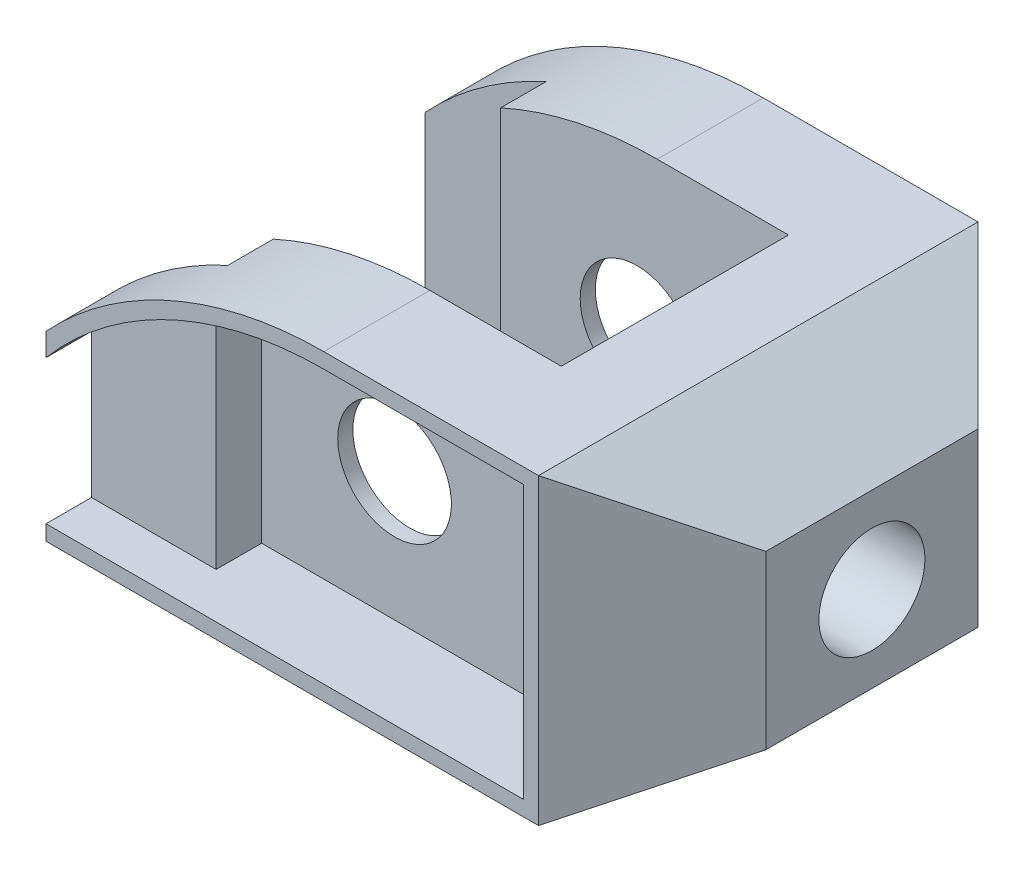
SolidWorks part; units mm, degrees
material "1060 Alloy"
ref_plane "Front Plane" through (0, 0, 0) normal (0, 0, 1) x (1, 0, 0)
ref_plane "Top Plane" through (0, 0, 0) normal (0, 1, 0) x (1, 0, 0)
ref_plane "Right Plane" through (0, 0, 0) normal (1, 0, 0) x (0, 0, -1)
sketch "Sketch1" plane through (0, 0, 0) normal (0, 0, 1) x (1, 0, 0)
  line L0 (0, 0) -> (65, 0)
  line L1 (65, 0) -> (80, 8.6603)
  line L2 (80, 8.6603) -> (80, 31.3397)
  line L3 (80, 31.3397) -> (65, 40)
  line L4 (65, 40) -> (36.6606, 40)
  line L5 (0, 24) -> (0, 0)
  arc A0 (36.6606, 40) -> (0, 24) centre (36.6606, -10) ccw
  circle A1 centre (34, 19) radius 7.5
  dimension "D7" = 50
  dimension "D10" = 15
  dimension "D1" = 65
  dimension "D2" = 30
  dimension "D3" = 30
  dimension "D4" = 40
  dimension "D5" = 15
  dimension "D6" = 24
  dimension "D8" = 19
  dimension "D9" = 31
extrude "Boss-Extrude1" add sketch "Sketch1" along normal blind 58
sketch "Sketch2" plane through (0, 40, 0) normal (0, 1, 0) x (1, 0, 0)
  line L0 (0, -8) -> (16, -8)
  line L1 (0, -58) -> (0, 0) construction
  line L2 (16, -8) -> (16, -14)
  line L3 (16, -14) -> (54, -14)
  line L4 (54, -14) -> (54, -44)
  line L5 (54, -44) -> (16, -44)
  line L6 (16, -44) -> (16, -50)
  line L7 (16, -50) -> (0, -50)
  line L8 (0, -58) -> (36.6606, -58) construction
  line L9 (65, -58) -> (65, 0) construction
  line L10 (36.6606, 0) -> (0, 0) construction
  line L11 (65, 0) -> (80, -15)
  line L12 (80, -58) -> (80, 0) construction
  line L13 (65, -58) -> (80, -43)
  line L14 (80, 0) -> (65, 0) construction
  line L15 (80, -58) -> (65, -58) construction
  line L16 (80, 0) -> (65, 0)
  line L17 (80, -58) -> (80, 0)
  line L18 (80, -58) -> (65, -58)
  line L19 (0, -58) -> (0, 0)
  line M11 (36.6606, 0) -> (36.6606, -58)
  dimension "D1" = 8
  dimension "D2" = 6
  dimension "D3" = 16
  dimension "D4" = 11
  dimension "D5" = 8
  dimension "D6" = 45
extrude "Cut-Extrude1" cut sketch "Sketch2" against normal through all contours L19 L7 L6 L5 L3 L2 L0 M11 | L5 L4 L3 M11 | L11 L17 L16 | L18 L17 L13 region at (16.7949, 40, 29) region at (45.3303, 40, 29) region at (75, 40, 5) region at (75, 40, 53)
sketch "Sketch3" plane through (80, 0, 0) normal (1, 0, 0) x (0, 0, -1)
  line L0 (-43, 8.6603) -> (-43, 31.3397) construction
  line L1 (-43, 31.3397) -> (-15, 31.3397) construction
  circle A0 centre (-29, 20) radius 7
  point P2 (0, 0)
  point P5 (-43, 20)
  point P6 (0, 0)
  point P9 (-29, 31.3397)
  dimension "D1" = 14
extrude "Cut-Extrude2" cut sketch "Sketch3" against normal through all
sketch "Sketch4" plane through (0, 0, 58) normal (0, 0, 1) x (1, 0, 0)
  line L1 (0, 24) -> (0, 0) construction
  line L2 (16.452, 33.5386) -> (16.452, 2)
  line L9 (0, 2) -> (63, 2)
  line L10 (63, 2) -> (63, 38)
  line L11 (63, 38) -> (36.6606, 38)
  line L12 (0, 2) -> (63, 2)
  line L13 (63, 2) -> (63, 38)
  line L14 (63, 38) -> (36.6606, 38)
  arc A5 (36.6606, 38) -> (1.4664, 22.64) centre (36.6606, -10) ccw
  arc A6 (36.6606, 38) -> (0, 20.9839) centre (36.6606, -10) ccw
  circle M5 centre (34, 19) radius 7.5
  line M10 (0, 24) -> (0, 0)
  dimension "D1" = 2
extrude "Cut-Extrude3" cut sketch "Sketch4" against normal blind 6 contours L2 A6 L12 M10 region at (8.8728, 15.3514, 58)
extrude "Cut-Extrude4" cut sketch "Sketch4<3>" against normal blind 12 contours L14 A6 L2 L12 L13 M5 region at (26.4399, 36.2968, 58)
sketch "Sketch4<3>" plane through (0, 0, 58) normal (0, 0, 1) x (1, 0, 0) same geometry as "Sketch4"
ref_plane "Plane1" through (0, 0, 29) normal (0, 0, 1) x (1, 0, 0)
mirror "Mirror1" about plane through (0, 0, 29) normal (0, 0, 1) of "Cut-Extrude3", "Cut-Extrude4"
